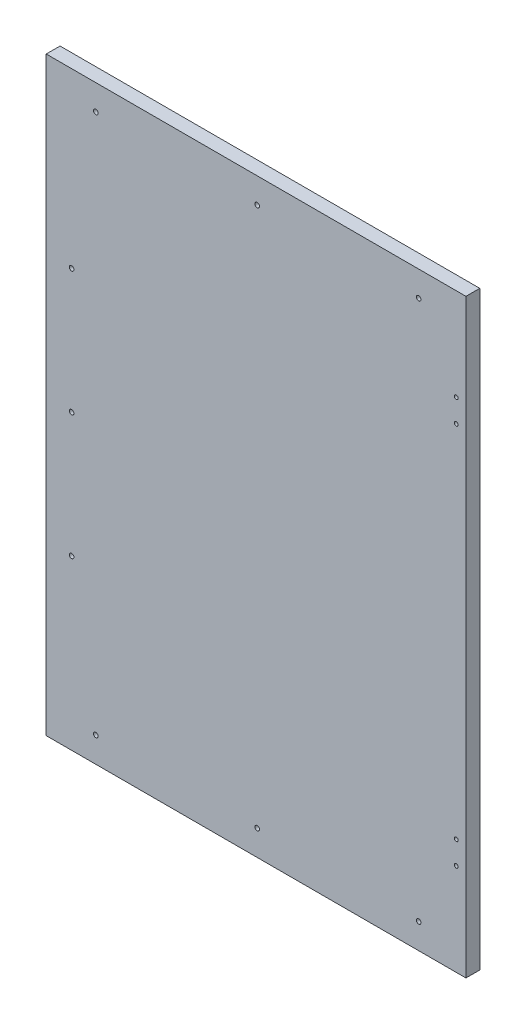
SolidWorks part; units mm, degrees
material "西洋杉"
ref_plane "正面" through (0, 0, 0) normal (0, 0, 1) x (1, 0, 0)
ref_plane "平面" through (0, 0, 0) normal (0, 1, 0) x (1, 0, 0)
ref_plane "右側面" through (0, 0, 0) normal (1, 0, 0) x (0, 0, -1)
sketch "ｽｹｯﾁ1" plane through (0, 0, 0) normal (0, 0, 1) x (1, 0, 0)
  line L1 (-227.5, 320) -> (227.5, 320)
  line L2 (-227.5, 320) -> (-227.5, -320)
  line L3 (-227.5, -320) -> (227.5, -320)
  line L4 (227.5, 320) -> (227.5, -320)
  line L5 (-227.5, 320) -> (227.5, -320) construction
  line L6 (-227.5, -320) -> (227.5, 320) construction
  point P0 (0, 0)
  dimension "D1" = 640
  dimension "D2" = 455
extrude "ﾎﾞｽ - 押し出し1" add sketch "ｽｹｯﾁ1" along normal blind 15
sketch "ｽｹｯﾁ2" plane through (0, 0, 15) normal (0, 0, 1) x (1, 0, 0)
  line L0 (-200, 292.5) -> (-200, -295) construction
  line L1 (-200, -295) -> (202.5, -295) construction
  line L2 (202.5, -295) -> (202.5, 292.5) construction
  line L3 (202.5, 292.5) -> (-200, 292.5) construction
  line L4 (-227.5, 320) -> (-227.5, -320) construction
  line L5 (227.5, 320) -> (-227.5, 320) construction
  line L6 (227.5, -320) -> (227.5, 320) construction
  line L7 (-227.5, -320) -> (227.5, -320) construction
  line L8 (-227.5, -320) -> (227.5, -320) construction
  line L9 (-227.5, 320) -> (-227.5, -320) construction
  circle A0 centre (-200, 132.5) radius 2.5
  circle A1 centre (-200, -2.5) radius 2.5
  circle A2 centre (-200, -137.5) radius 2.5
  circle A6 centre (1.25, 292.5) radius 2.5
  circle A7 centre (-173.75, 292.5) radius 2.5
  circle A8 centre (176.25, 292.5) radius 2.5
  circle A9 centre (150, 132.5) radius 2.5 [skipped]
  circle A10 centre (150, -2.5) radius 2.5 [skipped]
  circle A11 centre (150, -137.5) radius 2.5 [skipped]
  dimension "D5" = 5
  dimension "D11" = 5
  dimension "D12" = 5
  dimension "D13" = 5
  dimension "D14" = 175
  dimension "D15" = 175
  dimension "D1" = 27.5
  dimension "D2" = 27.5
  dimension "D3" = 25
  dimension "D4" = 25
  dimension "D6" = 160
  dimension "D7" = 640
  dimension "D8" = 455
  dimension "D9" = 3
  dimension "D10" = 2
extrude "ｶｯﾄ - 押し出し1" cut sketch "ｽｹｯﾁ2" against normal through all and the other way through all contours A2 | A1 | A0 region at (-200, -137.5, 15)
extrude "ｶｯﾄ - 押し出し2" cut sketch "ｽｹｯﾁ2<3>" against normal through all contours A7 | A6 | A8
sketch "ｽｹｯﾁ2<3>" plane through (0, 0, 15) normal (0, 0, 1) x (1, 0, 0) same geometry as "ｽｹｯﾁ2"
mirror "ﾐﾗｰ1" about plane through (0, 0, 0) normal (0, 1, 0) of "ｶｯﾄ - 押し出し2"
sketch "ｽｹｯﾁ3" plane through (0, 0, 15) normal (0, 0, 1) x (1, 0, 0)
  line L0 (217, 320) -> (217, -320) construction
  line L1 (227.5, 320) -> (-227.5, 320) construction
  line L2 (-227.5, -320) -> (227.5, -320) construction
  line L3 (227.5, -320) -> (227.5, 320) construction
  circle A0 centre (217, -220) radius 2.1
  circle A1 centre (217, -195) radius 2.1
  dimension "D4" = 4.2
  dimension "D5" = 4.2
  dimension "D1" = 10.5
  dimension "D2" = 25
  dimension "D3" = 100
extrude "ｶｯﾄ - 押し出し3" cut sketch "ｽｹｯﾁ3" against normal through all
mirror "ﾐﾗｰ2" about plane through (0, 0, 0) normal (0, 1, 0) of "ｶｯﾄ - 押し出し3"
equation "\"D4@ｽｹｯﾁ3\"=\"D5@ｽｹｯﾁ3\""
